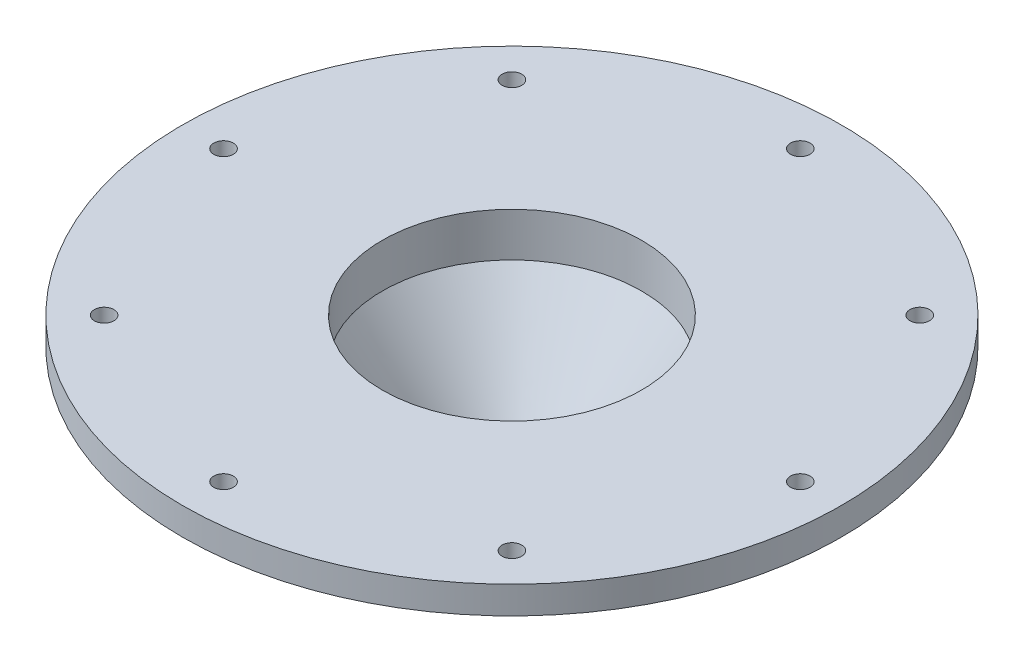
SolidWorks part; units mm, degrees
material "7075-T6 (SN)"
ref_plane "Front Plane" through (0, 0, 0) normal (0, 0, 1) x (1, 0, 0)
ref_plane "Top Plane" through (0, 0, 0) normal (0, 1, 0) x (1, 0, 0)
ref_plane "Right Plane" through (0, 0, 0) normal (1, 0, 0) x (0, 0, -1)
sketch "Sketch1" plane through (0, 0, 0) normal (0, 1, 0) x (1, 0, 0)
  circle A0 centre (0, 0) radius 38.1
  dimension "D1" = 76.2
extrude "Boss-Extrude1" add sketch "Sketch1" along normal blind 3.175
hole_wizard "Tap Drill for #4-40 Tap1" positions "Sketch3" profile "Sketch4" hole size "#4-40" standard "ANSI Inch" end condition through all
sketch "Sketch3" plane through (0, 0, 0) normal (0, -1, 0) x (-1, 0, 0)
  point P0 (0, -33.3375)
  dimension "D1" = 33.3375
sketch "Sketch4" plane through (0, 0, 33.3375) normal (1, 0, 0) x (0, 0, -1)
  line L0 (0, 0) -> (0, 3.175)
  line L1 (0, 3.175) -> (1.1303, 3.175)
  line L2 (1.1303, 3.175) -> (1.1303, 0)
  line L5 (1.1303, 0) -> (0, 0)
  line L11 (0, -6.35) -> (0, 107.95) construction
  dimension "Thru Hole Dia." = 2.2606
  dimension "Thru Hole Depth" = 3.175
pattern_circular "CirPattern1" count 8 over 360 about axis through (0, 0, 0) along (0, 1, 0) of "Tap Drill for #4-40 Tap1"
sketch "Sketch5" plane through (0, 0, 0) normal (0, -1, 0) x (1, 0, 0)
  circle A0 centre (0, 0) radius 25.4
  dimension "D1" = 50.8
extrude "Boss-Extrude2" add sketch "Sketch5" along normal blind 19.05
sketch "Sketch6" plane through (0, -19.05, 0) normal (0, -1, 0) x (1, 0, 0)
  circle A0 centre (0, 0) radius 5
  dimension "D1" = 10
extrude "Cut-Extrude1" cut sketch "Sketch6" against normal through all both and the other way through all
sketch "Sketch7" plane through (0, 3.175, 0) normal (0, 1, 0) x (1, 0, 0)
  circle A0 centre (0, 0) radius 15
  dimension "D1" = 30
extrude "Cut-Extrude2" cut sketch "Sketch7" against normal blind 5.08
sketch "Sketch8" plane through (0, -1.905, 0) normal (0, 1, 0) x (1, 0, 0)
  circle A0 centre (0, 0) radius 15
  circle A1 centre (0, 0) radius 15 construction
  dimension "D1" = 0
ref_plane "Plane1" through (0, -15.875, 0) normal (0, -1, 0) x (-1, 0, 0)
sketch "Sketch9" plane through (0, -15.875, 0) normal (0, -1, 0) x (-1, 0, 0)
  circle A0 centre (0, 0) radius 5
  circle A1 centre (0, 0) radius 5 construction
  dimension "D1" = 0
loft "Cut-Loft1" cut profiles "Sketch8", "Sketch9" connector at (0, -1.905, 15) connector at (-1.3659, -15.875, 4.8098)
sketch "Sketch10" plane through (0, 0, 0) normal (0, 0, 1) x (1, 0, 0)
  line L6 (0, 0) -> (0, -33.2378) construction
  line L7 (-25.4, 0) -> (-24.4, 0)
  line L8 (-25.4, 0) -> (25.4, 0) construction
  line L9 (-24.4, 0) -> (-8.4152, -19.05)
  line L10 (-25.4, -19.05) -> (25.4, -19.05) construction
  line L11 (-8.4152, -19.05) -> (-25.4, -19.05)
  line L12 (-25.4, -19.05) -> (-25.4, 0)
  dimension "D1" = 50
  dimension "D2" = 1
revolve "Cut-Revolve1" cut sketch "Sketch10" angle 360 about L6
